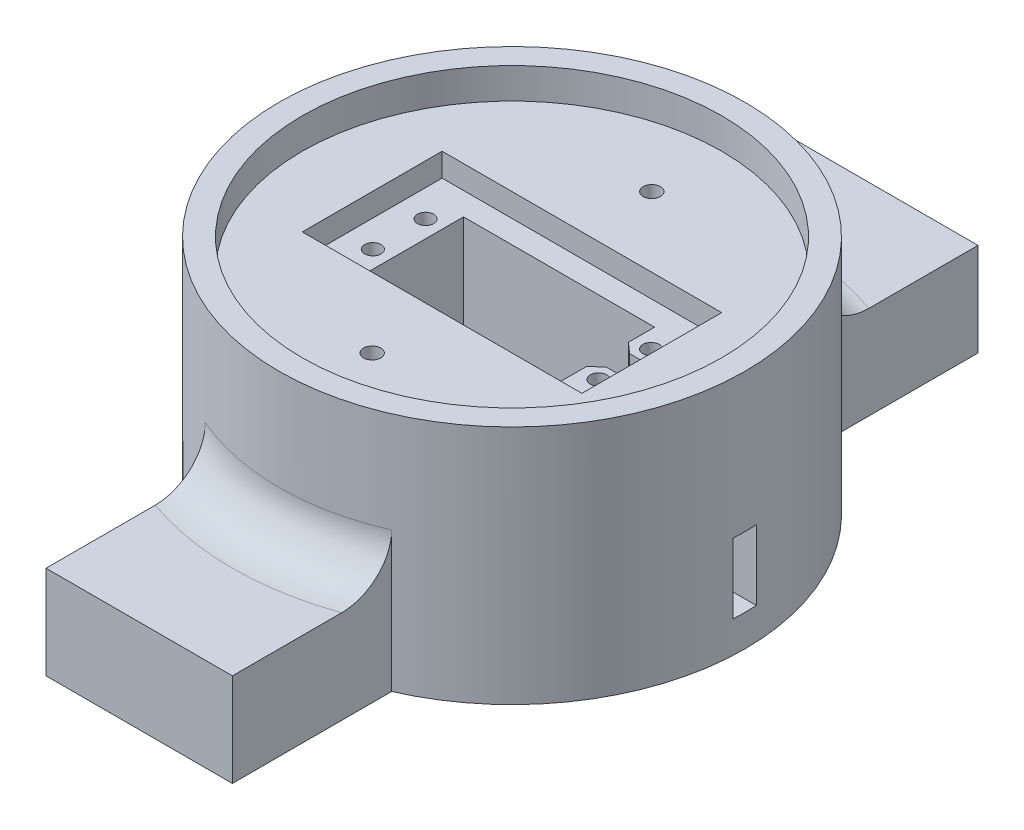
SolidWorks part; units mm, degrees
material "Plastique personnalisé"
ref_plane "Plan de face" through (0, 0, 0) normal (0, 0, 1) x (1, 0, 0)
ref_plane "Plan de dessus" through (0, 0, 0) normal (0, 1, 0) x (1, 0, 0)
ref_plane "Plan de droite" through (0, 0, 0) normal (1, 0, 0) x (0, 0, -1)
sketch "Esquisse1" plane through (0, 0, 0) normal (0, 1, 0) x (1, 0, 0)
  circle A0 centre (0, 0) radius 50
  dimension "D1" = 100
extrude "Boss.-Extru.1" add sketch "Esquisse1" along normal blind 45
sketch "Esquisse2" plane through (0, 45, 0) normal (0, 1, 0) x (1, 0, 0)
  line L0 (-15, 0) -> (-33.4, 0) construction
  line L1 (0, 0) -> (0, 10.1) construction
  line L2 (0, 0) -> (0, -35.3248) construction
  line L3 (-62.0573, 0) -> (62.0573, 0) construction
  line L4 (-20.5, -10.1) -> (20.5, 10.1) construction
  line L5 (-20.5, 10.1) -> (20.5, 10.1)
  line L6 (-20.5, 10.1) -> (-20.5, -10.1)
  line L7 (-20.5, -10.1) -> (20.5, -10.1)
  line L8 (20.5, 10.1) -> (20.5, 4.5)
  line L9 (-24.2, -35.3248) -> (-24.2, -6.3196) construction
  line L10 (20.5, -4.5) -> (20.5, -10.1)
  line L11 (22.7361, -2.5) -> (28.5, -2.5)
  line L13 (28.5, -2.5) -> (28.5, 2.5)
  line L14 (-30, -15) -> (30, 15) construction
  line L15 (-30, 15) -> (30, 15)
  line L16 (-30, 15) -> (-30, -15)
  line L17 (-30, -15) -> (30, -15)
  line L18 (30, 15) -> (30, -15)
  line L19 (20.5, 4.5) -> (22.7361, 2.5)
  line L20 (20.5, -4.5) -> (22.7361, -2.5)
  line L21 (22.7361, 2.5) -> (28.5, 2.5)
  circle A0 centre (-24.2, 5.65) radius 1.75
  circle A1 centre (-24.2, -5.65) radius 1.75
  circle A2 centre (24.2, -5.65) radius 1.75
  circle A3 centre (24.2, 5.65) radius 1.75
  circle A4 centre (0, 0) radius 50
  circle A5 centre (0, 0) radius 45
  point P3 (-24.2, 0)
  point P8 (0, 0)
  point P13 (0, 0)
  point P16 (0, 0)
  point P26 (0, 0)
  point P28 (0, 0)
  circle M2 centre (0, 0) radius 50
  dimension "D5" = 3.5
  dimension "D13" = 100
  dimension "D14" = 90
  dimension "D1" = 15
  dimension "D2" = 20.2
  dimension "D3" = 41
  dimension "D4" = 24.2
  dimension "D6" = 5.65
  dimension "D7" = 5
  dimension "D8" = 8
  dimension "D9" = 131.81
  dimension "D10" = 3.7
  dimension "D11" = 60
  dimension "D12" = 30
  dimension "D15" = 3
extrude "Enlèv. mat.-Extru.2" cut sketch "Esquisse2" against normal blind 5 contours L18 L17 L16 L15
extrude "Enlèv. mat.-Extru.4" cut sketch "Esquisse2<3>" against normal blind 38.2 contours L5 L8 L19 L21 L13 L11 L20 L10 L7 L6
sketch "Esquisse2<3>" plane through (0, 45, 0) normal (0, 1, 0) x (1, 0, 0) same geometry as "Esquisse2"
extrude "Boss.-Extru.2" add sketch "Esquisse2<4>" along normal blind 6.6 contours A5 M2 region at (-48.5858, 45, 0)
sketch "Esquisse2<4>" plane through (0, 45, 0) normal (0, 1, 0) x (1, 0, 0) same geometry as "Esquisse2"
extrude "Enlèv. mat.-Extru.5" cut sketch "Esquisse2<5>" against normal blind 10 contours A2 | A3 | A0 | A1 region at (-24.2, 45, -5.65) region at (-24.2, 45, 5.65) region at (24.2, 45, 5.65) region at (24.2, 45, -5.65)
sketch "Esquisse2<5>" plane through (0, 45, 0) normal (0, 1, 0) x (1, 0, 0) same geometry as "Esquisse2"
sketch "Esquisse3" plane through (0, 45, 0) normal (0, 1, 0) x (1, 0, 0)
  line L0 (0, 45) -> (0, -45) construction
  line L1 (-44.9949, 0) -> (49.7535, 0) construction
  circle A0 centre (0, 0) radius 45 construction
  circle A1 centre (0, 30) radius 1.85
  circle A2 centre (0, -30) radius 1.85
  dimension "D1" = 3.7
  dimension "D2" = 30
extrude "Enlèv. mat.-Extru.6" cut sketch "Esquisse3" against normal blind 10
ref_plane "Plan1" through (0, 0, 50) normal (0, 0, 1) x (1, 0, 0)
sketch "Esquisse4" plane through (0, 0, 50) normal (0, 0, 1) x (1, 0, 0)
  line L0 (50, 0) -> (-50, 0) construction
  line L1 (-20, 0) -> (20, 0)
  line L2 (-20, 0) -> (-20, 20)
  line L3 (-20, 20) -> (20, 20)
  line L4 (20, 0) -> (20, 20)
  line L6 (-50, 0) -> (50, 0) construction
  line L7 (-50, 51.6) -> (-50, 0) construction
  point P6 (0, 0)
  point P12 (0, 0)
  dimension "D1" = 40
  dimension "D2" = 20
extrude "Boss.-Extru.3" add sketch "Esquisse4" along normal blind 30 and the other way blind 13
ref_plane "Plan2" through (0, 0, 0) normal (0, 0, 1) x (1, 0, 0)
mirror "Symétrie1" about plane through (0, 0, 0) normal (0, 0, 1) of "Boss.-Extru.3"
fillet "Congé1" radius 10 2 edges at (0, 20, 50) (0, 20, -50)
sketch "Esquisse5" plane through (28.5, 0, 0) normal (-1, 0, 0) x (0, 0, 1)
  line L6 (2.5, 6.8) -> (2.5, 40) construction
  line L7 (-2.5, 6.8) -> (2.5, 6.8)
  line L8 (-2.5, 6.8) -> (-2.5, 21.8)
  line L9 (-2.5, 21.8) -> (2.5, 21.8)
  line L10 (2.5, 6.8) -> (2.5, 21.8)
  dimension "D1" = 15
extrude "Enlèv. mat.-Extru.7" cut sketch "Esquisse5" against normal through all
